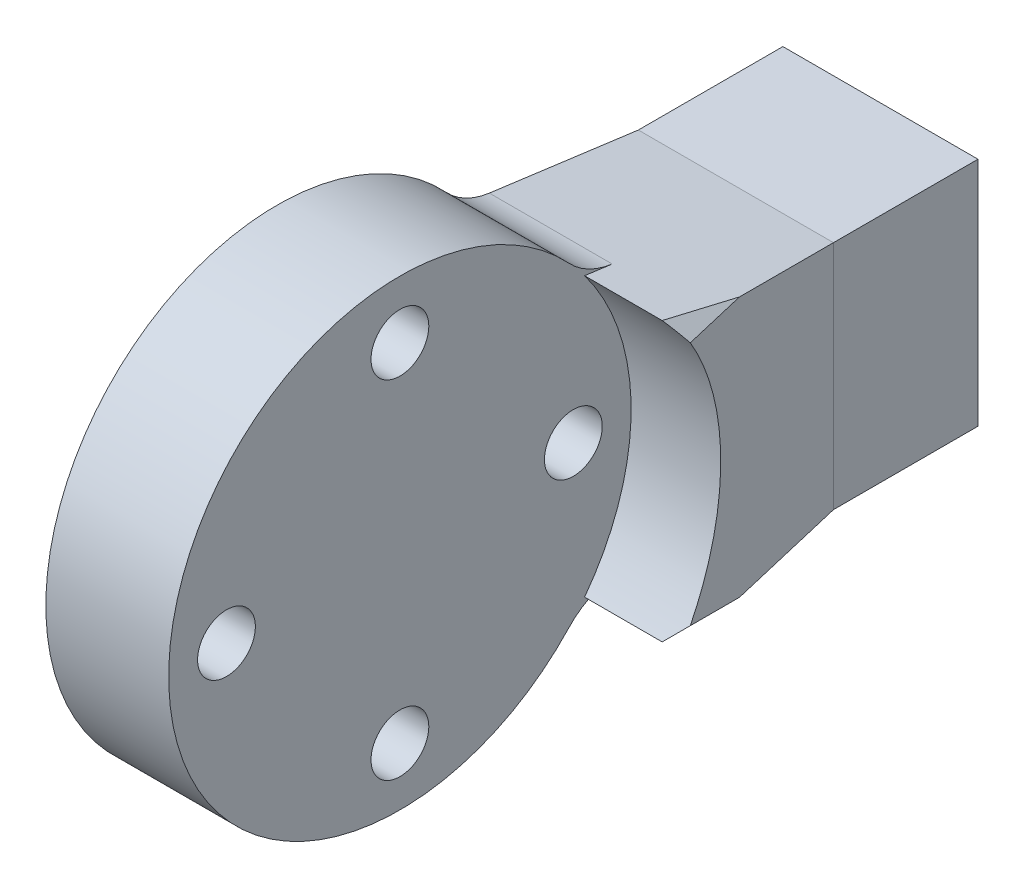
SolidWorks part; units mm, degrees
ref_plane "Front Plane" through (0, 0, 0) normal (0, 0, 1) x (1, 0, 0)
ref_plane "Top Plane" through (0, 0, 0) normal (0, 1, 0) x (1, 0, 0)
ref_plane "Right Plane" through (0, 0, 0) normal (1, 0, 0) x (0, 0, -1)
sketch "Sketch1" plane through (0, 0, 0) normal (1, 0, 0) x (0, -1, 0)
  line L1 (-10, 0) -> (10, 0)
  line L2 (-10, 0) -> (-10, 25)
  line L3 (-10, 25) -> (10, 25)
  line L4 (10, 0) -> (10, 25)
  circle A0 centre (0, 0) radius 4.5
  circle A1 centre (0, 0) radius 10
  dimension "D1" = 9
  dimension "D2" = 20
  dimension "D3" = 25
extrude "Boss-Extrude1" add sketch "Sketch1" along normal blind 16 contours A1 L4 L3 L2 | L1 A1 A0 | L1 A1 A0 region at (0, 0, -4.8368) region at (0, 0, 4.8368) region at (0, 0, -16.2817)
chamfer "Chamfer1" distance 15 distance2 2 3 edges at (8, -10, -25) (8, 10, -25) (16, 0, -25) first distance on face at (8, -10, -12.5) first distance on face at (8, 10, -12.5) first distance on face at (16, 0, -10)
sketch "Sketch2" plane through (0, 0, -25) normal (0, 0, -1) x (-1, 0, 0)
  line L0 (0, 8) -> (0, -8) construction
  line L1 (-16, 10) -> (0, 10) construction
  circle A0 centre (-8, 0) radius 3
  dimension "D1" = 6
  dimension "D2" = 8
  dimension "D3" = 10
extrude "Cut-Extrude1" cut sketch "Sketch2" against normal blind 15
chamfer "Chamfer2" distance 2 angle 45 6 edges at (0, 0, 10) (16, 10, -5) (0, 10, -5) (0, -10, -5) (16, -10, -5) (16, 0, 10)
thread "Thread1" pitch 1.5 method cut profile "Thread Profile1" start angle 0, offset 1, length 0, pitch 1.5, diameter 9
ref_plane "Plane1" through (-1, 0, -4.5) normal (0, -1, 0) x (0, 0, -1)
sketch "Thread Profile1" plane through (-1, 0, -4.5) normal (0, -1, 0) x (0, 0, -1)
  line L0 (0, 0) -> (0, 1.5) construction
  line L1 (0, 0) -> (0.8119, 0.4687)
  line L2 (0.8119, 0.4687) -> (0.8119, 0.6562)
  line L3 (0.8119, 0.6562) -> (0, 1.125)
  line L4 (0.8119, 0.5625) -> (0, 0.5625) construction
  line L11 (0, 0) -> (0, 1.125)
  point P2 (0, 0)
  dimension "Pitch" = 1.5
  dimension "Profile_Angle" = 60
  dimension "Profile_Land" = 0.1875
  dimension "Profile_Height" = 0.8119
sketch "Sketch5" plane through (0, 0, 0) normal (-1, 0, 0) x (0, 0, 1)
  circle A0 centre (0, 0) radius 7
  dimension "D1" = 14
extrude "Boss-Extrude2" add sketch "Sketch5" against normal up to surface (16 mm away) up to face at (16, 0, -3)
sketch "Sketch10" plane through (0, 0, -25) normal (0, 0, -1) x (-1, 0, 0)
  line L4 (-14, 8) -> (-14, -8)
  line L5 (-14, -8) -> (0, -8)
  line L6 (0, -8) -> (0, 8)
  line L7 (0, 8) -> (-14, 8)
  line L8 (-14, 8) -> (-14, -8)
  line L9 (-14, -8) -> (0, -8)
  line L10 (0, -8) -> (0, 8)
  line L11 (0, 8) -> (-14, 8)
  circle A0 centre (-8, 0) radius 3 construction
  circle A1 centre (-8, 0) radius 3
  dimension "D1" = 0
extrude "Boss-Extrude3" add sketch "Sketch10" along normal blind 10
sketch "Sketch11" plane through (0, 0, -10) normal (0, 0, -1) x (-1, 0, 0)
  circle A1 centre (-8, 0) radius 3
  circle A2 centre (-8, 0) radius 3
  dimension "D1" = 0
extrude "Boss-Extrude4" add sketch "Sketch11" along normal blind 10
sketch "Sketch12" plane through (16, 0, 0) normal (1, 0, 0) x (0, 0, -1)
  circle A0 centre (0, 0) radius 16
  dimension "D1" = 32
extrude "Cut-Extrude2" cut sketch "Sketch12" against normal blind 7
sketch "Sketch13" plane through (9, 0, 0) normal (1, 0, 0) x (0, 0, -1)
  circle A0 centre (0, 0) radius 16
extrude "Boss-Extrude5" add sketch "Sketch13" against normal up to surface (9 mm away) up to face at (0, 0, -18.6667)
sketch "Sketch14" plane through (0, 0, 0) normal (-1, 0, 0) x (0, 0, 1)
  line L0 (-25, -8) -> (-13.8564, -8) construction
  line L1 (-25, -8) -> (-13.8564, -8)
  line L2 (-13.8564, 8) -> (-25, 8) construction
  line L3 (-13.8564, 8) -> (-25, 8)
  line L4 (-25, 8) -> (-12.7777, 9.6296) construction
  line L5 (-25, 8) -> (-12.7777, 9.6296)
  line L6 (-12.7777, -9.6296) -> (-25, -8) construction
  line L7 (-12.7777, -9.6296) -> (-25, -8)
  arc A0 (-13.8564, -8) -> (-13.8564, 8) centre (0, 0) ccw construction
  arc A1 (-13.8564, -8) -> (-12.7777, -9.6296) centre (0, 0) ccw
  arc A2 (-12.7777, 9.6296) -> (-13.8564, 8) centre (0, 0) ccw
extrude "Boss-Extrude6" add sketch "Sketch14" against normal up to surface (9 mm away) up to face at (9, 0, 0)
sketch "Sketch15" plane through (9, 0, 0) normal (1, 0, 0) x (0, 0, -1)
  line L0 (0, 0) -> (12, 0) construction
  line L1 (0, 0) -> (0, 12) construction
  line L2 (-12, 0) -> (0, 0) construction
  line L3 (0, -12) -> (0, 0) construction
  circle A0 centre (12, 0) radius 2
  circle A1 centre (0, 12) radius 2
  circle A2 centre (-12, 0) radius 2
  circle A3 centre (0, -12) radius 2
  dimension "D1" = 12
  dimension "D2" = 4
  dimension "D3" = 4
  dimension "D4" = 12
  dimension "D5" = 4
  dimension "D6" = 12
  dimension "D7" = 4
  dimension "D8" = 12
extrude "Cut-Extrude3" cut sketch "Sketch15" against normal blind 20
fillet "Fillet1" radius 5 1 edges at (4.5, -9.6296, -12.7777)
fillet "Fillet2" radius 5 1 edges at (4.5, 9.6296, -12.7777)
sketch "Sketch16" plane through (0, 0, 0) normal (-1, 0, 0) x (0, 0, 1)
  line L5 (-14.6893, 9.3748) -> (-25, 8)
  line L6 (-25, 8) -> (-35, 8)
  line L7 (-35, 8) -> (-35, -8)
  line L8 (-35, -8) -> (-25, -8)
  line L9 (-25, -8) -> (-14.6893, -9.3748)
  line L10 (-14.6893, 9.3748) -> (-25, 8)
  line L11 (-25, 8) -> (-35, 8)
  line L12 (-35, 8) -> (-35, -8)
  line L13 (-35, -8) -> (-25, -8)
  line L14 (-25, -8) -> (-14.6893, -9.3748)
  arc A3 (-11.6953, -10.9188) -> (-11.6953, 10.9188) centre (0, 0) ccw
  arc A4 (-14.6893, 9.3748) -> (-11.6953, 10.9188) centre (-15.3501, 14.3309) ccw
  arc A5 (-11.6953, -10.9188) -> (-14.6893, -9.3748) centre (-15.3501, -14.3309) ccw
  arc A6 (-11.6953, -10.9188) -> (-11.6953, 10.9188) centre (0, 0) ccw
  arc A7 (-14.6893, 9.3748) -> (-11.6953, 10.9188) centre (-15.3501, 14.3309) ccw
  arc A8 (-11.6953, -10.9188) -> (-14.6893, -9.3748) centre (-15.3501, -14.3309) ccw
  dimension "D1" = 0
extrude "Cut-Extrude4" cut sketch "Sketch16" against normal blind 0.5
sketch "Sketch17" plane through (0, 0, -35) normal (0, 0, -1) x (-1, 0, 0)
  circle A0 centre (-8, 0) radius 4
  dimension "D1" = 8
extrude "Cut-Extrude5" cut sketch "Sketch17" against normal blind 15
